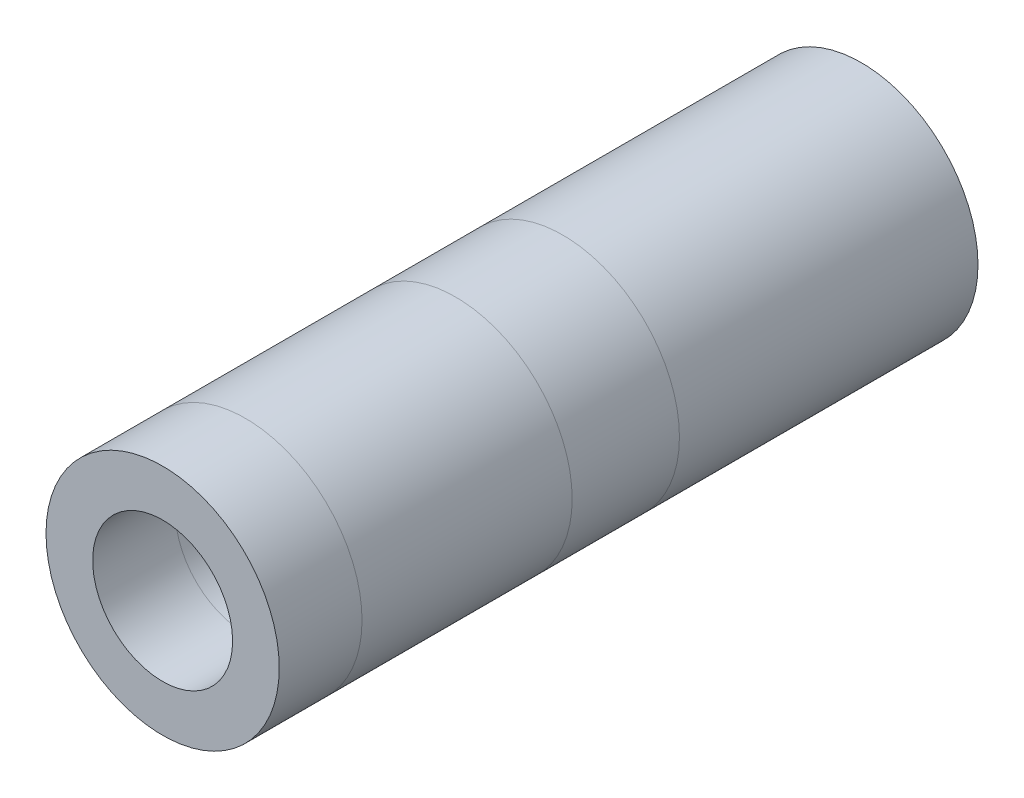
SolidWorks part; units mm, degrees
material "Silicon Rubber"
ref_plane "X-Y Datum" through (0, 0, 0) normal (0, 0, 1) x (1, 0, 0)
ref_plane "X-Z Datum" through (0, 0, 0) normal (0, 1, 0) x (1, 0, 0)
ref_plane "Y-Z Datum" through (0, 0, 0) normal (1, 0, 0) x (0, 0, -1)
sketch3d "3DSketch1"
  line L0 (0, 0, 0) -> (0, 0, -7.3)
  line L1 (0, 0, -7.3) -> (0, 0, -27.62)
  line L2 (0, 0, 14.302) -> (0, 0, 19.9354)
  line L3 (0, 0, 14.302) -> (0, 0, 0)
  arc A0 (-5, 0, 0) -> (5, 0, 0) centre (0, 0, 0) ccw construction
  arc A1 (-5, 0, 0) -> (5, 0, 0) centre (0, 0, 0) ccw construction
  arc A2 (-5, 0, -7.3) -> (5, 0, -7.3) centre (0, 0, -7.3) ccw construction
  arc A3 (-5, 0, -7.3) -> (5, 0, -7.3) centre (0, 0, -7.3) ccw construction
  circle A8 centre (0, 0, 19.9354) radius 5 construction
  circle A9 centre (0, 0, 19.9354) radius 5 construction
  point P3 (0, 0, -5)
  point P4 (0, 0, -5)
  point P8 (0, 0, -12.3)
  point P9 (0, 0, -12.3)
  point P14 (0, 0, 14.9354)
  point P17 (0, 0, 14.9354)
  dimension "D1" = 20.32
sweep "Sweep1" add path "3DSketch1" circular profile diameter 15.875 parameters "D3"=15.875
sweep "Cut-Sweep1" cut path "3DSketch1<2>" circular profile diameter 9.525 parameters "D3"=9.525
sketch3d "3DSketch1<2>" same geometry as "3DSketch1"
